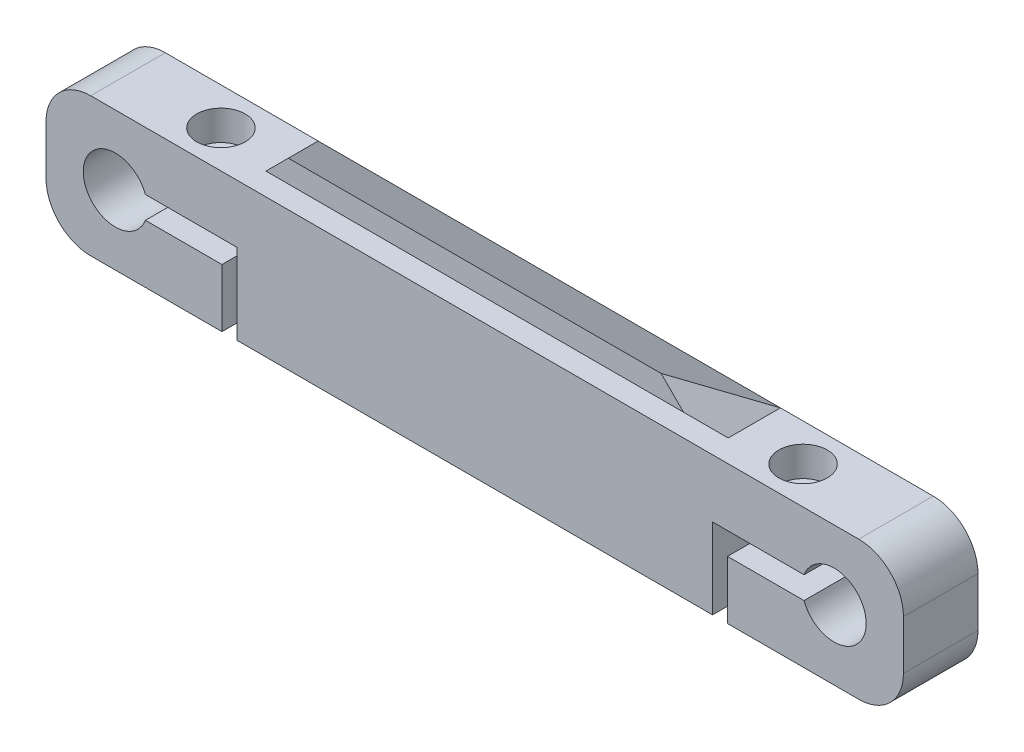
SolidWorks part; units mm, degrees
ref_plane "Alzado" through (0, 0, 0) normal (0, 0, 1) x (1, 0, 0)
ref_plane "Planta" through (0, 0, 0) normal (0, 1, 0) x (1, 0, 0)
ref_plane "Vista lateral" through (0, 0, 0) normal (1, 0, 0) x (0, 0, -1)
sketch "Croquis1" plane through (0, 0, 0) normal (0, 0, 1) x (1, 0, 0)
  line L0 (-48.2, 0) -> (48.2, 0) construction
  line L1 (-51.5, 9.3) -> (51.5, 9.3)
  line L2 (-57.5, 3.3) -> (-57.5, -3.3)
  line L3 (-51.5, -9.3) -> (51.5, -9.3)
  line L4 (57.5, 3.3) -> (57.5, -3.3)
  line L5 (-57.5, 9.3) -> (57.5, -9.3) construction
  line L6 (-57.5, -9.3) -> (57.5, 9.3) construction
  line L7 (-45.2641, 1.5) -> (-31.9, 1.5)
  line L8 (-31.9, 1.5) -> (-31.9, -9.3)
  line L9 (33.9, -1.5) -> (33.9, -9.3)
  line L10 (0, 9.3) -> (0, -9.3) construction
  line L11 (-46.3533, -1.5) -> (-33.9, -1.5)
  line L12 (-33.9, -1.5) -> (-33.9, -9.3)
  line L13 (31.9, 1.5) -> (31.9, -9.3)
  line L14 (46.3533, -1.5) -> (33.9, -1.5)
  line L15 (45.2641, 1.5) -> (31.9, 1.5)
  line L16 (-57.439, 24.5025) -> (-57.439, -43.5519) construction
  line L18 (58.0207, -15.7775) -> (58.0207, 36.8628) construction
  circle A0 centre (-48.2, 0) radius 4.3
  circle A1 centre (48.2, 0) radius 4.3
  arc A2 (51.5, 9.3) -> (57.5, 3.3) centre (51.5, 3.3) cw
  arc A3 (57.5, -3.3) -> (51.5, -9.3) centre (51.5, -3.3) cw
  arc A4 (-57.5, -3.3) -> (-51.5, -9.3) centre (-51.5, -3.3) ccw
  arc A5 (-51.5, 9.3) -> (-57.5, 3.3) centre (-51.5, 3.3) ccw
  point P0 (0, 0)
  dimension "D3" = 8.6
  dimension "D4" = 8.6
  dimension "D7" = 6
  dimension "D8" = 1.5
  dimension "D1" = 96.4
  dimension "D2" = 48.2
  dimension "D5" = 115
  dimension "D6" = 18.6
  dimension "D9" = 1.5
  dimension "D10" = 9.3
  dimension "D11" = 16.3
  dimension "D12" = 2
extrude "Saliente-Extruir1" add sketch "Croquis1" along normal blind 10 contours L1 A5 L2 A4 L3 A0 A1 A3 L4 A2 region at (0, 0.0892, 0)
sketch "Croquis2" plane through (0, 1.5, 0) normal (0, -1, 0) x (1, 0, 0)
  line L1 (0, 10) -> (0, 0) construction
  line L3 (-44.1701, 10) -> (-44.1701, 0) construction
  line L4 (-33.9, 10) -> (-33.9, 0) construction
  circle A0 centre (-39.0351, 5) radius 1.9
  circle A1 centre (39.0351, 5) radius 1.9
  dimension "D2" = 3.8
  dimension "D1" = 5.135
  dimension "D3" = 5.1351
extrude "Cortar-Extruir1" cut sketch "Croquis2" against normal mid plane 50
sketch "Croquis5" plane through (0, 9.3, 0) normal (0, 1, 0) x (1, 0, 0)
  circle A0 centre (-39.0351, -5) radius 3.25
  circle A1 centre (39.0351, -5) radius 3.25
extrude "Cortar-Extruir3" cut sketch "Croquis5" against normal blind 4
sketch "Croquis6" plane through (0, -9.3, 0) normal (0, -1, 0) x (-1, 0, 0)
  line L1 (42.4992, -5) -> (40.7672, -2)
  line L2 (40.7672, -2) -> (37.3031, -2)
  line L3 (37.3031, -2) -> (35.571, -5)
  line L4 (35.571, -5) -> (37.3031, -8)
  line L5 (37.3031, -8) -> (40.7672, -8)
  line L6 (40.7672, -8) -> (42.4992, -5)
  line L7 (-42.4992, -5) -> (-40.7672, -8)
  line L8 (-40.7672, -8) -> (-37.3031, -8)
  line L9 (-37.3031, -8) -> (-35.571, -5)
  line L10 (-35.571, -5) -> (-37.3031, -2)
  line L11 (-37.3031, -2) -> (-40.7672, -2)
  line L12 (-40.7672, -2) -> (-42.4992, -5)
  circle A0 centre (39.0351, -5) radius 3 construction
  circle A1 centre (-39.0351, -5) radius 3 construction
  dimension "D1" = 6
  dimension "D2" = 6
extrude "Cortar-Extruir4" cut sketch "Croquis6" against normal blind 4.25
ref_plane "Plano1" through (0, 0, 0) normal (-1, 0, 0) x (0, 0, 1)
sketch "Croquis7" plane through (0, 0, 0) normal (-1, 0, 0) x (0, 0, 1)
  line L0 (10, 9.3) -> (10, 18.1053) construction
  line L1 (0, 9.3) -> (10, 15.3)
  line L2 (10, 15.3) -> (10, 12.3)
  line L4 (10, 9.3) -> (0, 9.3) construction
  line L6 (10, 12.3) -> (7, 9.3)
  line L7 (7, 9.3) -> (0, 9.3)
  dimension "D1" = 6
  dimension "D2" = 3
  dimension "D3" = 45
extrude "Saliente-Extruir2" add sketch "Croquis7" along normal mid plane 50
chamfer "Chaflán2" distance 6 angle 45 2 edges at (-25, 9.3, 3.5) (25, 9.3, 3.5)
sketch "Croquis8" plane through (0, -9.3, 0) normal (0, -1, 0) x (1, 0, 0)
  line L0 (-31.9, 0) -> (-35.9415, -7)
  line L1 (-34.2094, -10) -> (34.2094, -10)
  line L2 (35.9415, -7) -> (31.9, 0)
  line L3 (31.9, 0) -> (-31.9, 0)
  line L4 (-51.5, 0) -> (-33.9, 0) construction
  line L5 (33.9, 0) -> (51.5, 0) construction
  arc A0 (-35.9415, -7) -> (-34.2094, -10) centre (-34.2094, -8) ccw
  arc A1 (34.2094, -10) -> (35.9415, -7) centre (34.2094, -8) ccw
  dimension "D4" = 2
  dimension "D1" = 10
  dimension "D2" = 60
  dimension "D3" = 60
extrude "Saliente-Extruir3" add sketch "Croquis8" against normal blind 5
sketch "Croquis9" plane through (0, -4.3, 0) normal (0, 1, 0) x (1, 0, 0)
  line L0 (-34.4981, 4.5) -> (34.4981, 4.5) construction
  circle A0 centre (0, 4.5) radius 1.9
  circle A1 centre (-29.4981, 4.5) radius 1.9
  circle A2 centre (-14.7481, 4.5) radius 1.9
  circle A3 centre (14.7481, 4.5) radius 1.9
  circle A4 centre (29.4981, 4.5) radius 1.9
  dimension "D3" = 5
  dimension "D4" = 5
  dimension "D5" = 14.75
  dimension "D6" = 14.75
extrude "Cortar-Extruir5" cut sketch "Croquis9" against normal through all
sketch "Croquis10" plane through (0, -9.3, 0) normal (0, -1, 0) x (1, 0, 0)
  line L1 (3.4064, -4.5) -> (1.7032, -1.55)
  line L2 (1.7032, -1.55) -> (-1.7032, -1.55)
  line L3 (-1.7032, -1.55) -> (-3.4064, -4.5)
  line L4 (-3.4064, -4.5) -> (-1.7032, -7.45)
  line L5 (-1.7032, -7.45) -> (1.7032, -7.45)
  line L6 (1.7032, -7.45) -> (3.4064, -4.5)
  line L7 (-11.3417, -4.5) -> (-13.0449, -1.55)
  line L8 (-13.0449, -1.55) -> (-16.4513, -1.55)
  line L9 (-16.4513, -1.55) -> (-18.1544, -4.5)
  line L10 (-18.1544, -4.5) -> (-16.4513, -7.45)
  line L11 (-16.4513, -7.45) -> (-13.0449, -7.45)
  line L12 (-13.0449, -7.45) -> (-11.3417, -4.5)
  line L13 (-26.0917, -4.5) -> (-27.7949, -1.55)
  line L14 (-27.7949, -1.55) -> (-31.2013, -1.55)
  line L15 (-31.2013, -1.55) -> (-32.9044, -4.5)
  line L16 (-32.9044, -4.5) -> (-31.2013, -7.45)
  line L17 (-31.2013, -7.45) -> (-27.7949, -7.45)
  line L18 (-27.7949, -7.45) -> (-26.0917, -4.5)
  line L19 (18.1544, -4.5) -> (16.4513, -1.55)
  line L20 (16.4513, -1.55) -> (13.0449, -1.55)
  line L21 (13.0449, -1.55) -> (11.3417, -4.5)
  line L22 (11.3417, -4.5) -> (13.0449, -7.45)
  line L23 (13.0449, -7.45) -> (16.4513, -7.45)
  line L24 (16.4513, -7.45) -> (18.1544, -4.5)
  line L25 (32.9044, -4.5) -> (31.2013, -1.55)
  line L26 (31.2013, -1.55) -> (27.7949, -1.55)
  line L27 (27.7949, -1.55) -> (26.0917, -4.5)
  line L28 (26.0917, -4.5) -> (27.7949, -7.45)
  line L29 (27.7949, -7.45) -> (31.2013, -7.45)
  line L30 (31.2013, -7.45) -> (32.9044, -4.5)
  circle A0 centre (0, -4.5) radius 2.95 construction
  circle A1 centre (-14.7481, -4.5) radius 2.95 construction
  circle A2 centre (-29.4981, -4.5) radius 2.95 construction
  circle A3 centre (14.7481, -4.5) radius 2.95 construction
  circle A4 centre (29.4981, -4.5) radius 2.95 construction
  dimension "D1" = 5.9
  dimension "D2" = 5.9
  dimension "D3" = 5.9
  dimension "D4" = 5.9
  dimension "D5" = 5.9
extrude "Cortar-Extruir6" cut sketch "Croquis10" against normal blind 2.75
sketch "Croquis11" plane through (0, -4.3, 0) normal (0, 1, 0) x (1, 0, 0)
  line L0 (-31.9, 0) -> (-32.766, 1.5)
  line L1 (-31.9, 0) -> (-35.9415, 7) construction
  line L2 (-32.766, 1.5) -> (32.766, 1.5)
  line L3 (35.9415, 7) -> (31.9, 0) construction
  line L4 (32.766, 1.5) -> (31.9, 0)
  line L5 (31.9, 0) -> (-31.9, 0)
  dimension "D1" = 1.5
extrude "Saliente-Extruir4" add sketch "Croquis11" along normal blind 0.2
